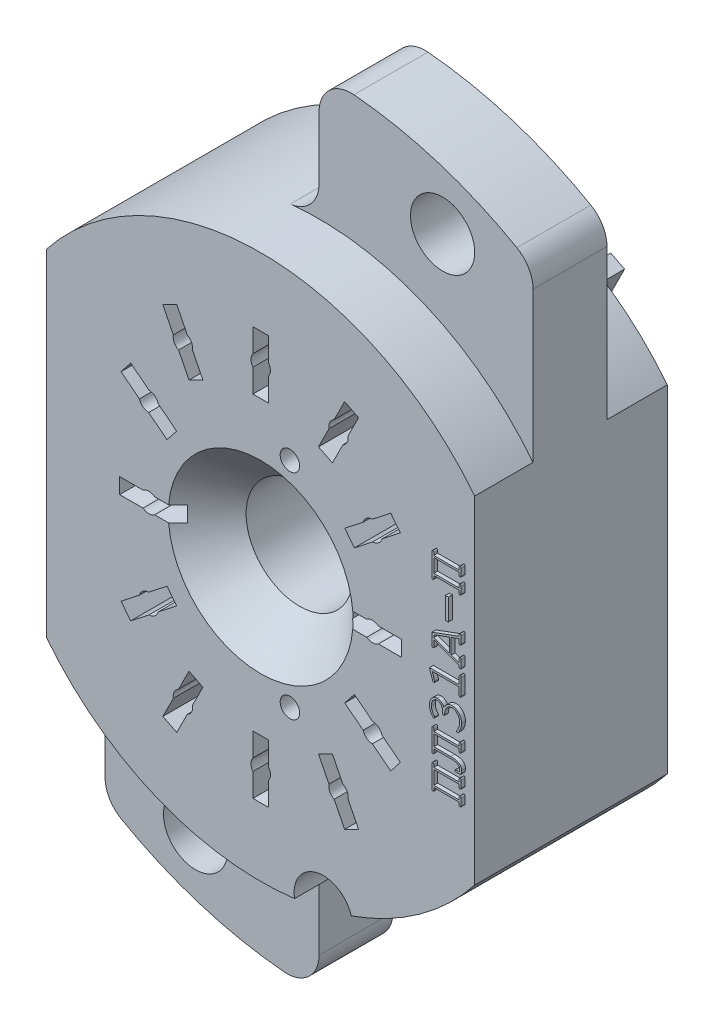
SolidWorks part; units mm, degrees
ref_plane "Front Plane" through (0, 0, 0) normal (0, 0, 1) x (1, 0, 0)
ref_plane "Top Plane" through (0, 0, 0) normal (0, 1, 0) x (1, 0, 0)
ref_plane "Right Plane" through (0, 0, 0) normal (1, 0, 0) x (0, 0, -1)
sketch "Sketch2" plane through (0, 0, 0) normal (0, 0, 1) x (1, 0, 0)
  line L0 (-31.5495, -8.6603) -> (-31.5495, -17.2988)
  line L2 (-31.5495, 8.6603) -> (-31.5495, -8.6603)
  line L4 (-9.5495, 8.6603) -> (-9.5495, -8.6603)
  line L5 (-20.5495, -20.5) -> (-20.5495, -14)
  line L6 (-9.5495, 8.6603) -> (-9.5495, 17.2988)
  line L7 (-20.5495, 14) -> (-20.5495, 20.5)
  arc A0 (-20.5495, -14) -> (-9.5495, -8.6603) centre (-20.5495, 0) ccw
  arc A1 (-20.5495, 14) -> (-31.5495, 8.6603) centre (-20.5495, 0) ccw
  arc A2 (-31.5495, -17.2988) -> (-20.5495, -20.5) centre (-20.5495, 0) ccw
  arc A4 (-9.5495, 17.2988) -> (-20.5495, 20.5) centre (-20.5495, 0) ccw
  arc A6 (-31.5495, -17.2988) -> (-20.5495, -20.5) centre (-20.5495, 0) ccw
  point P9 (-31.5495, -8.6603)
  point P10 (-31.5495, -17.2988)
  point P11 (-20.5495, -20.5)
  dimension "D1" = 28
  dimension "D3" = 41
  dimension "D6" = 11
  dimension "D2" = 22
  dimension "D4" = 17.3205
  dimension "D5" = 11
  dimension "D7" = 8.6386
extrude "Boss-Extrude1" add sketch "Sketch2" along normal blind 3.8 contours L6 A4 L7 A1 L2 L0 A2 L5 A0 L4 region at (-20.5495, 0, 0)
sketch "Sketch3" plane through (0, 0, 0) normal (0, 0, 1) x (1, 0, 0)
  line L0 (-31.5495, -8.6603) -> (-31.5495, -17.2988)
  line L2 (-31.5495, 8.6603) -> (-31.5495, -8.6603)
  line L4 (-9.5495, 8.6603) -> (-9.5495, -8.6603)
  line L5 (-20.5495, -20.5) -> (-20.5495, -14)
  line L6 (-9.5495, 8.6603) -> (-9.5495, 17.2988)
  line L7 (-20.5495, 14) -> (-20.5495, 20.5)
  arc A0 (-20.5495, -14) -> (-9.5495, -8.6603) centre (-20.5495, 0) ccw
  arc A1 (-20.5495, 14) -> (-31.5495, 8.6603) centre (-20.5495, 0) ccw
  arc A2 (-31.5495, -17.2988) -> (-20.5495, -20.5) centre (-20.5495, 0) ccw
  arc A4 (-9.5495, 17.2988) -> (-20.5495, 20.5) centre (-20.5495, 0) ccw
  arc A6 (-31.5495, -17.2988) -> (-20.5495, -20.5) centre (-20.5495, 0) ccw
  point P9 (-31.5495, -8.6603)
  point P10 (-31.5495, -17.2988)
  point P11 (-20.5495, -20.5)
  dimension "D1" = 28
  dimension "D3" = 41
  dimension "D6" = 11
  dimension "D2" = 22
  dimension "D4" = 17.3205
  dimension "D5" = 11
  dimension "D7" = 8.6386
sketch "Sketch4" plane through (0, 0, 3.8) normal (0, 0, 1) x (1, 0, 0)
  line L0 (-9.5495, 8.6603) -> (-9.5495, -8.6603)
  line L1 (-31.5495, -8.6603) -> (-31.5495, 8.6603)
  arc A0 (-9.5495, 8.6603) -> (-31.5495, 8.6603) centre (-20.5495, 0) ccw
  arc A1 (-31.5495, -8.6603) -> (-9.5495, -8.6603) centre (-20.5495, 0) ccw
extrude "Boss-Extrude2" add sketch "Sketch4" along normal blind 3
sketch "Sketch5" plane through (0, 0, 0) normal (0, 0, -1) x (-1, 0, 0)
  line L0 (31.5495, 8.6603) -> (31.5495, -8.6603)
  line L1 (9.5495, 8.6603) -> (9.5495, -8.6603)
  arc A0 (31.5495, 8.6603) -> (9.5495, 8.6603) centre (20.5495, 0) ccw
  arc A1 (9.5495, -8.6603) -> (31.5495, -8.6603) centre (20.5495, 0) ccw
extrude "Boss-Extrude3" add sketch "Sketch5" along normal blind 3.1
sketch "Sketch6" plane through (0, 0, 3.8) normal (0, 0, 1) x (1, 0, 0)
  line L0 (-9.5495, 8.6603) -> (-9.5495, 17.2988) construction
  circle A0 centre (-14.1995, 16.5) radius 1.65
  dimension "D1" = 3.3
  dimension "D2" = 4.65
  dimension "D3" = 2.5
extrude "Cut-Extrude1" cut sketch "Sketch6" against normal up to surface (3.8 mm away) up to face at (-14.8391, 15.6269, 0)
sketch "Sketch12" plane through (0, 0, 0) normal (0, 1, 0) x (1, 0, 0)
  line L0 (-20.5495, -6.8) -> (-20.5495, 3.1) construction
  line L1 (-31.5495, -6.8) -> (-9.5495, -6.8) construction
  line L2 (-9.5495, 3.1) -> (-31.5495, 3.1) construction
pattern_circular "CirPattern1" count 2 every 180 about axis through (-20.5495, 0, 6.8) along (0, 0, -1) of "Cut-Extrude1"
sketch "Sketch13" plane through (0, 0, 6.8) normal (0, 0, 1) x (1, 0, 0)
  line L0 (-19.0495, 5.5) -> (-19.0495, -5.5) construction
  line L1 (-20.5495, 9) -> (-20.5495, -9) construction
  line L2 (-16.5495, 8) -> (-16.5495, -8) construction
  line L3 (-14.7995, 4.5) -> (-14.7995, -4.5) construction
  line L4 (-20.5495, 0) -> (-16.5495, 8) construction
  line L5 (-20.5495, 0) -> (-14.7995, 4.5) construction
  line L6 (-20.5495, 0) -> (-14.7995, 0) construction
  line L7 (-16.2365, 9.5205) -> (-16.7732, 8.4472)
  line L8 (-20.9495, 10.5) -> (-20.1495, 10.5)
  line L9 (-20.9495, 10.5) -> (-20.9495, 9.3)
  line L10 (-20.9495, 7.5) -> (-20.1495, 7.5)
  line L11 (-20.1495, 10.5) -> (-20.1495, 9.3)
  line L14 (-16.2365, 9.5205) -> (-15.521, 9.1628)
  line L15 (-17.5781, 6.8372) -> (-16.8626, 6.4795)
  line L16 (-15.521, 9.1628) -> (-16.0576, 8.0894)
  line L17 (-16.2365, 9.5205) -> (-16.6504, 7.5103) construction
  line L18 (-17.5781, 6.8372) -> (-15.521, 9.1628) construction
  line L19 (-13.3718, 5.1095) -> (-14.3168, 4.3699)
  line L20 (-13.3718, 5.1095) -> (-13.8648, 5.7395)
  line L21 (-15.7343, 3.2605) -> (-16.2273, 3.8905)
  line L22 (-13.8648, 5.7395) -> (-14.8098, 4.9999)
  line L23 (-13.3718, 5.1095) -> (-16.2273, 3.8905) construction
  line L24 (-15.7343, 3.2605) -> (-13.8648, 5.7395) construction
  line L25 (-16.2995, -0.4) -> (-15.0995, -0.4)
  line L26 (-16.2995, -0.4) -> (-16.2995, 0.4)
  line L27 (-13.2995, -0.4) -> (-13.2995, 0.4)
  line L28 (-16.2995, 0.4) -> (-15.0995, 0.4)
  line L29 (-16.2995, -0.4) -> (-13.2995, 0.4) construction
  line L30 (-13.2995, -0.4) -> (-16.2995, 0.4) construction
  line L31 (-20.9495, 8.7) -> (-20.9495, 7.5)
  line L32 (-20.1495, 8.7) -> (-20.1495, 7.5)
  line L33 (-16.3259, 7.5528) -> (-16.8626, 6.4795)
  line L34 (-17.0415, 7.9106) -> (-17.5781, 6.8372)
  line L35 (-15.2823, 4.6301) -> (-16.2273, 3.8905)
  line L36 (-14.7893, 4.0001) -> (-15.7343, 3.2605)
  line L37 (-14.4995, 0.4) -> (-13.2995, 0.4)
  line L38 (-14.4995, -0.4) -> (-13.2995, -0.4)
  line L39 (-20.9495, -10.5) -> (-20.9495, -9.3)
  line L40 (-20.9495, -8.7) -> (-20.9495, -7.5)
  line L41 (-20.9495, -7.5) -> (-20.1495, -7.5)
  line L42 (-20.1495, -8.7) -> (-20.1495, -7.5)
  line L43 (-20.1495, -10.5) -> (-20.1495, -9.3)
  line L44 (-20.9495, -10.5) -> (-20.1495, -10.5)
  line L45 (-16.2365, -9.5205) -> (-15.521, -9.1628)
  line L46 (-15.521, -9.1628) -> (-16.0576, -8.0894)
  line L47 (-16.3259, -7.5528) -> (-16.8626, -6.4795)
  line L48 (-17.5781, -6.8372) -> (-16.8626, -6.4795)
  line L49 (-17.0415, -7.9106) -> (-17.5781, -6.8372)
  line L50 (-16.2365, -9.5205) -> (-16.7732, -8.4472)
  line L51 (-14.7893, -4.0001) -> (-15.7343, -3.2605)
  line L52 (-15.7343, -3.2605) -> (-16.2273, -3.8905)
  line L53 (-15.2823, -4.6301) -> (-16.2273, -3.8905)
  line L54 (-13.8648, -5.7395) -> (-14.8098, -4.9999)
  line L55 (-13.3718, -5.1095) -> (-13.8648, -5.7395)
  line L56 (-13.3718, -5.1095) -> (-14.3168, -4.3699)
  line L57 (-24.8626, -9.5205) -> (-24.3259, -8.4472)
  line L58 (-24.0576, -7.9106) -> (-23.521, -6.8372)
  line L59 (-23.521, -6.8372) -> (-24.2365, -6.4795)
  line L60 (-24.7732, -7.5528) -> (-24.2365, -6.4795)
  line L61 (-25.5781, -9.1628) -> (-25.0415, -8.0894)
  line L62 (-24.8626, -9.5205) -> (-25.5781, -9.1628)
  line L63 (-27.7273, -5.1095) -> (-26.7823, -4.3699)
  line L64 (-27.7273, -5.1095) -> (-27.2343, -5.7395)
  line L65 (-27.2343, -5.7395) -> (-26.2893, -4.9999)
  line L66 (-25.8168, -4.6301) -> (-24.8718, -3.8905)
  line L67 (-25.3648, -3.2605) -> (-24.8718, -3.8905)
  line L68 (-26.3098, -4.0001) -> (-25.3648, -3.2605)
  line L69 (-24.7995, -0.4) -> (-24.7995, 0.4)
  line L70 (-24.7995, 0.4) -> (-25.9995, 0.4)
  line L71 (-26.5995, 0.4) -> (-27.7995, 0.4)
  line L72 (-27.7995, -0.4) -> (-27.7995, 0.4)
  line L73 (-26.5995, -0.4) -> (-27.7995, -0.4)
  line L74 (-24.7995, -0.4) -> (-25.9995, -0.4)
  line L75 (-26.3098, 4.0001) -> (-25.3648, 3.2605)
  line L76 (-25.3648, 3.2605) -> (-24.8718, 3.8905)
  line L77 (-25.8168, 4.6301) -> (-24.8718, 3.8905)
  line L78 (-27.2343, 5.7395) -> (-26.2893, 4.9999)
  line L79 (-27.7273, 5.1095) -> (-27.2343, 5.7395)
  line L80 (-27.7273, 5.1095) -> (-26.7823, 4.3699)
  line L81 (-24.8626, 9.5205) -> (-25.5781, 9.1628)
  line L82 (-25.5781, 9.1628) -> (-25.0415, 8.0894)
  line L83 (-24.7732, 7.5528) -> (-24.2365, 6.4795)
  line L84 (-23.521, 6.8372) -> (-24.2365, 6.4795)
  line L85 (-24.0576, 7.9106) -> (-23.521, 6.8372)
  line L86 (-24.8626, 9.5205) -> (-24.3259, 8.4472)
  circle A0 centre (-20.5495, 0) radius 2.75
  circle A1 centre (-19.0495, 5.5) radius 0.5
  circle A2 centre (-19.0495, -5.5) radius 0.5
  arc A3 (-20.9495, 9.3) -> (-20.9495, 8.7) centre (-20.5495, 9) ccw
  arc A4 (-16.7732, 8.4472) -> (-17.0415, 7.9106) centre (-16.5495, 8) ccw
  arc A5 (-14.8098, 4.9999) -> (-15.2823, 4.6301) centre (-14.7995, 4.5) ccw
  arc A6 (-14.4995, 0.4) -> (-15.0995, 0.4) centre (-14.7995, 0) ccw
  arc A15 (-16.3259, 7.5528) -> (-16.0576, 8.0894) centre (-16.5495, 8) ccw
  arc A16 (-20.1495, 8.7) -> (-20.1495, 9.3) centre (-20.5495, 9) ccw
  arc A17 (-14.7893, 4.0001) -> (-14.3168, 4.3699) centre (-14.7995, 4.5) ccw
  arc A18 (-15.0995, -0.4) -> (-14.4995, -0.4) centre (-14.7995, 0) ccw
  arc A19 (-20.9495, -9.3) -> (-20.9495, -8.7) centre (-20.5495, -9) cw
  arc A20 (-20.1495, -8.7) -> (-20.1495, -9.3) centre (-20.5495, -9) cw
  arc A21 (-16.3259, -7.5528) -> (-16.0576, -8.0894) centre (-16.5495, -8) cw
  arc A22 (-16.7732, -8.4472) -> (-17.0415, -7.9106) centre (-16.5495, -8) cw
  arc A23 (-14.8098, -4.9999) -> (-15.2823, -4.6301) centre (-14.7995, -4.5) cw
  arc A24 (-14.7893, -4.0001) -> (-14.3168, -4.3699) centre (-14.7995, -4.5) cw
  arc A25 (-24.3259, -8.4472) -> (-24.0576, -7.9106) centre (-24.5495, -8) ccw
  arc A26 (-24.7732, -7.5528) -> (-25.0415, -8.0894) centre (-24.5495, -8) ccw
  arc A27 (-26.3098, -4.0001) -> (-26.7823, -4.3699) centre (-26.2995, -4.5) ccw
  arc A28 (-26.2893, -4.9999) -> (-25.8168, -4.6301) centre (-26.2995, -4.5) ccw
  arc A29 (-26.5995, 0.4) -> (-25.9995, 0.4) centre (-26.2995, 0) cw
  arc A30 (-25.9995, -0.4) -> (-26.5995, -0.4) centre (-26.2995, 0) cw
  arc A31 (-26.2893, 4.9999) -> (-25.8168, 4.6301) centre (-26.2995, 4.5) cw
  arc A32 (-26.3098, 4.0001) -> (-26.7823, 4.3699) centre (-26.2995, 4.5) cw
  arc A33 (-24.7732, 7.5528) -> (-25.0415, 8.0894) centre (-24.5495, 8) cw
  arc A34 (-24.3259, 8.4472) -> (-24.0576, 7.9106) centre (-24.5495, 8) cw
  point P7 (-19.0495, 0)
  point P26 (-20.5495, 0)
  point P27 (-16.5495, 0)
  point P28 (-14.7995, 0)
  point P51 (0, 0)
  point P64 (-16.1583, 3.9445)
  point P122 (0, 0)
  point P123 (-32.1854, -3.1928)
  dimension "D1" = 5.5
  dimension "D2" = 1
  dimension "D5" = 1
  dimension "D11" = 0.8
  dimension "D3" = 5.5
  dimension "D4" = 1.5
  dimension "D6" = 5.75
  dimension "D7" = 18
  dimension "D8" = 16
  dimension "D9" = 9
  dimension "D10" = 4
  dimension "D12" = 3
  dimension "D13" = 1.2
extrude "Cut-Extrude2" cut sketch "Sketch13" against normal up to surface (9.9 mm away) up to face at (-20.5495, 0, -3.1)
sketch "Sketch14" plane through (0, 0, 6.8) normal (0, 0, 1) x (1, 0, 0)
  line L0 (-20.5495, 0) -> (-20.5495, -13.0412) construction
  line L1 (-20.5495, 0) -> (-15.1022, -10.8946) construction
  line L2 (-20.5495, -9.6587) -> (-16.2301, -8.639) construction
  line L3 (-20.5495, 0) -> (-16.7012, -16.3019) construction
  line L4 (-16.2365, -9.5205) -> (-15.521, -9.1628) construction
  line L5 (-20.9495, -10.5) -> (-20.1495, -10.5) construction
  circle A0 centre (-17.333, -13.6255) radius 1.5
  arc A1 (-20.5495, -14) -> (-9.5495, -8.6603) centre (-20.5495, 0) ccw construction
  circle A2 centre (-20.5495, 0) radius 9.6587 construction
  point P10 (-20.5495, -9.6587)
  point P11 (-16.2301, -8.639)
  point P14 (-20.5495, -10.5)
  point P16 (-17.333, -13.6255)
  point P17 (-20.5495, -10.315)
  point P18 (-15.8787, -9.3416)
  point P23 (-20.5495, -10.5)
  point P24 (-15.8787, -9.3416)
  point P25 (-15.4105, -10.807)
  point P26 (-15.1022, -10.8946)
  dimension "D1" = 3
extrude "Cut-Extrude3" cut sketch "Sketch14" against normal blind 3
chamfer "Chamfer1" distance 2 angle 45 1 edges at (-17.7995, 0, 6.8)
fillet "Fillet1" radius 1.65 6 edges at (-31.5495, -17.2988, 1.9) (-20.5495, -20.5, 1.9) (-20.5495, -14, 1.9) (-20.5495, 14, 1.9) (-20.5495, 20.5, 1.9) (-9.5495, 17.2988, 1.9)
sketch "Sketch15" plane through (0, 0, -3.1) normal (0, 0, -1) x (-1, 0, 0)
  line L0 (24.639, 9.0733) -> (23.7446, 7.2845)
  line L1 (20.1495, 10) -> (20.9495, 10)
  line L2 (20.1495, 10) -> (20.1495, 8)
  line L3 (20.1495, 8) -> (20.9495, 8)
  line L4 (20.9495, 10) -> (20.9495, 8)
  line L5 (24.639, 9.0733) -> (25.3545, 8.7155)
  line L6 (20.1495, 9.3) -> (20.1495, 10.5) construction
  line L7 (20.9495, 10.5) -> (20.9495, 9.3) construction
  line L8 (20.9495, 10.5) -> (20.9495, 7.5) construction
  line L9 (23.7446, 7.2845) -> (24.4601, 6.9267)
  line L10 (25.3545, 8.7155) -> (24.4601, 6.9267)
  line L11 (24.3259, 8.4472) -> (24.8626, 9.5205) construction
  line L12 (23.521, 6.8372) -> (24.0576, 7.9106) construction
  line L13 (26.8405, 5.4313) -> (25.2655, 4.1987)
  line L14 (24.7732, 7.5528) -> (24.2365, 6.4795) construction
  line L15 (24.8626, 9.5205) -> (23.521, 6.8372) construction
  line L16 (26.8405, 5.4313) -> (27.3336, 4.8013)
  line L17 (25.2655, 4.1987) -> (25.7586, 3.5687)
  line L18 (27.3336, 4.8013) -> (25.7586, 3.5687)
  line L19 (26.2893, 4.9999) -> (27.2343, 5.7395) construction
  line L20 (24.8718, 3.8905) -> (25.8168, 4.6301) construction
  line L21 (27.7995, 0.4) -> (24.7995, 0.4) construction
  line L22 (27.7273, 5.1095) -> (26.7823, 4.3699) construction
  line L23 (24.8718, 3.8905) -> (27.2343, 5.7395) construction
  line L24 (27.2995, 0.4) -> (25.2995, 0.4)
  line L25 (27.2995, 0.4) -> (27.2995, -0.4)
  line L26 (25.2995, 0.4) -> (25.2995, -0.4)
  line L27 (27.2995, -0.4) -> (25.2995, -0.4)
  line L28 (26.5995, 0.4) -> (27.7995, 0.4) construction
  line L29 (24.7995, 0.4) -> (25.9995, 0.4) construction
  line L30 (20.5495, 0) -> (20.5495, 9) construction
  line L31 (27.7995, -0.4) -> (26.5995, -0.4) construction
  line L32 (20.5495, 0) -> (24.5495, 8) construction
  line L33 (20.5495, 0) -> (26.2995, 4.5) construction
  line L34 (20.5495, 0) -> (26.2995, 0) construction
  line L35 (25.2655, -4.1987) -> (25.7586, -3.5687)
  line L36 (27.3336, -4.8013) -> (25.7586, -3.5687)
  line L37 (26.8405, -5.4313) -> (27.3336, -4.8013)
  line L38 (26.8405, -5.4313) -> (25.2655, -4.1987)
  line L39 (23.7446, -7.2845) -> (24.4601, -6.9267)
  line L40 (25.3545, -8.7155) -> (24.4601, -6.9267)
  line L41 (24.639, -9.0733) -> (25.3545, -8.7155)
  line L42 (24.639, -9.0733) -> (23.7446, -7.2845)
  line L43 (20.1495, -8) -> (20.9495, -8)
  line L44 (20.9495, -10) -> (20.9495, -8)
  line L45 (20.1495, -10) -> (20.9495, -10)
  line L46 (20.1495, -10) -> (20.1495, -8)
  line L47 (16.4601, -9.0733) -> (17.3545, -7.2845)
  line L48 (16.4601, -9.0733) -> (15.7446, -8.7155)
  line L49 (15.7446, -8.7155) -> (16.639, -6.9267)
  line L50 (17.3545, -7.2845) -> (16.639, -6.9267)
  line L51 (14.2586, -5.4313) -> (15.8336, -4.1987)
  line L52 (14.2586, -5.4313) -> (13.7655, -4.8013)
  line L53 (13.7655, -4.8013) -> (15.3405, -3.5687)
  line L54 (15.8336, -4.1987) -> (15.3405, -3.5687)
  line L55 (15.7995, 0.4) -> (15.7995, -0.4)
  line L56 (13.7995, -0.4) -> (15.7995, -0.4)
  line L57 (13.7995, 0.4) -> (13.7995, -0.4)
  line L58 (13.7995, 0.4) -> (15.7995, 0.4)
  line L59 (15.8336, 4.1987) -> (15.3405, 3.5687)
  line L60 (13.7655, 4.8013) -> (15.3405, 3.5687)
  line L61 (14.2586, 5.4313) -> (13.7655, 4.8013)
  line L62 (14.2586, 5.4313) -> (15.8336, 4.1987)
  line L63 (17.3545, 7.2845) -> (16.639, 6.9267)
  line L64 (15.7446, 8.7155) -> (16.639, 6.9267)
  line L65 (16.4601, 9.0733) -> (15.7446, 8.7155)
  line L66 (16.4601, 9.0733) -> (17.3545, 7.2845)
  point P8 (20.9495, 9)
  point P13 (20.9495, 9)
  point P28 (24.1918, 8.1789)
  point P29 (24.1918, 8.1789)
  point P44 (26.053, 4.815)
  point P45 (26.053, 4.815)
  point P60 (26.2995, 0.4)
  point P61 (26.2995, 0.4)
  dimension "D1" = 2
extrude "Boss-Extrude4" add sketch "Sketch15" along normal blind 4 separate body
sketch "Sketch16" plane through (0, 0, 6.8) normal (0, 0, 1) x (1, 0, 0)
  line L0 (-10.0495, -9.2601) -> (-10.0495, 9.2601) construction
  line L1 (-9.5495, -8.6603) -> (-9.5495, 8.6603) construction
  arc A0 (-15.8937, -13.2031) -> (-9.5495, -8.6603) centre (-20.5495, 0) ccw construction
  arc A2 (-9.5495, 8.6603) -> (-22.0256, 13.922) centre (-20.5495, 0) ccw construction
  text T0 "ПЛ31А-П" font "Courier New" height 1.5
  point P5 (-10.0495, 8.0519)
  point P6 (-10.0495, -2.7157)
  point P7 (-10.0495, -4.7017)
  point P8 (-3.6421, 0.2632)
  point P9 (0, 0)
  point P10 (-11.1204, -4.7017)
  point P11 (-10.0495, -2.2503)
  point P12 (-10.0495, -3.988)
  point P13 (-10.0495, -7.2772)
  point P14 (-10.0495, -12.6455)
  point P15 (-10.0495, -6.998)
  point P16 (-10.0495, -9.2601)
  point P20 (-10.0495, 9.2601)
  point P21 (-10.0495, -4.9733)
  point P22 (-10.0495, -2.2507)
  point P23 (-10.0495, -0.8158)
  point P24 (-4.9764, -5.5085)
  point P25 (0, 0)
  point P27 (-10.0495, 9.2601)
  point P28 (-10.0495, 2.0171)
  point P29 (-10.0495, 3.8567)
  point P30 (-10.0495, 5.6963)
  point P31 (-10.0495, 6.8)
  point P32 (-10.0495, 9.2601)
  dimension "D1" = 0.5
extrude "Boss-Extrude5" add sketch "Sketch16" along normal blind 0.2
